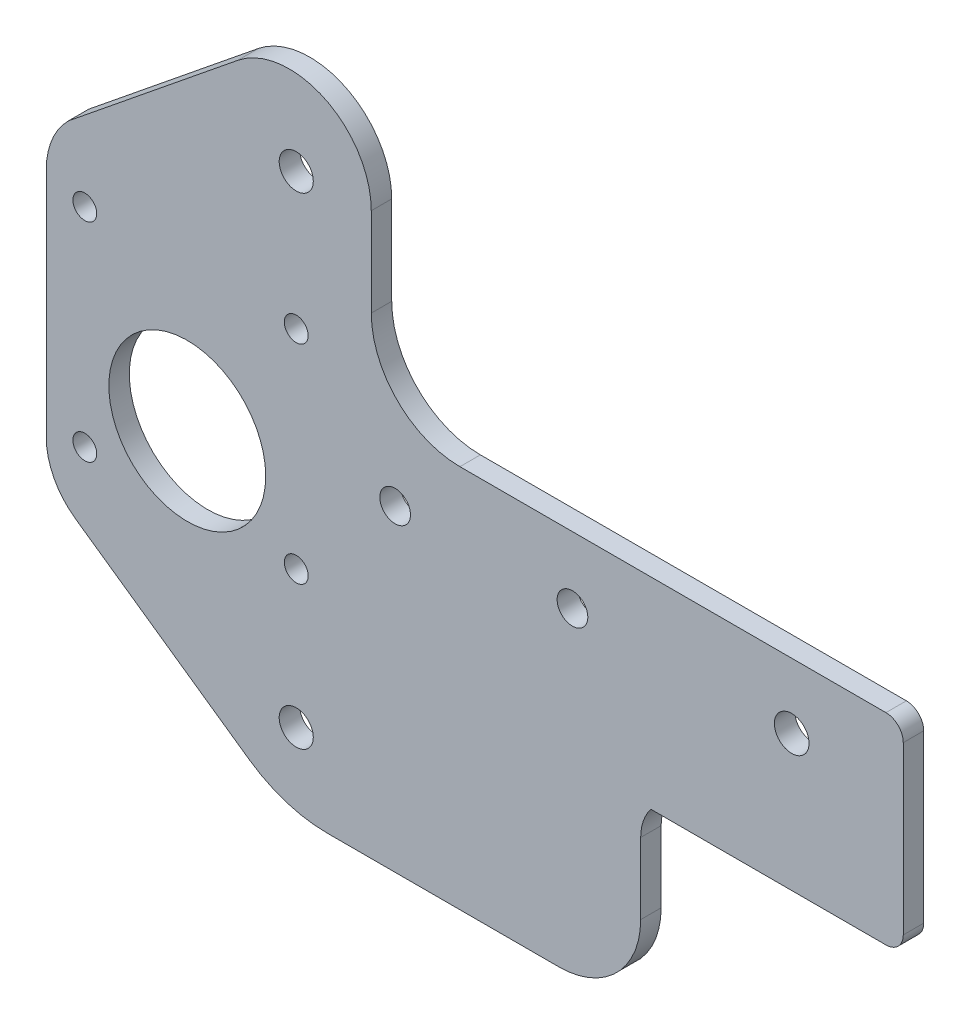
SolidWorks part; units mm, degrees
ref_plane "Front Plane" through (0, 0, 0) normal (0, 0, 1) x (1, 0, 0)
ref_plane "Top Plane" through (0, 0, 0) normal (0, 1, 0) x (1, 0, 0)
ref_plane "Right Plane" through (0, 0, 0) normal (1, 0, 0) x (0, 0, -1)
sketch "Sketch1" plane through (0, 0, 0) normal (0, 0, 1) x (1, 0, 0)
  line L0 (0, 0) -> (0, -29.5)
  line L1 (0, -29.5) -> (-37, -29.5)
  line L2 (0, 0) -> (-65, 0)
  line L3 (-78, 13) -> (-78, 26)
  line L4 (-97.5518, 35.3258) -> (-122.4205, 15.1875)
  line L5 (-125.65, 7.4017) -> (-125.65, -26.5983)
  line L6 (-89, 5.5) -> (-89, -25) construction
  line L7 (-120, 5.5) -> (-89, 5.5) construction
  line L8 (-121.3858, -34.7898) -> (-95.8858, -52.6451)
  line L9 (-84.4142, -56.2621) -> (-50.5, -56.2621)
  line L10 (-38.5, -44.2621) -> (-38.5, -33.8301)
  line L11 (-104.5, -9.75) -> (-104.5, 5.5) construction
  line L12 (-104.5, -9.75) -> (-89, -9.75) construction
  arc A0 (-78, 13) -> (-65, 0) centre (-65, 13) ccw
  arc A1 (-78, 26) -> (-97.5518, 35.3258) centre (-90, 26) ccw
  arc A2 (-122.4205, 15.1875) -> (-125.65, 7.4017) centre (-114.65, 7.4017) ccw
  arc A3 (-125.65, -26.5983) -> (-121.3858, -34.7898) centre (-115.65, -26.5983) ccw
  arc A4 (-95.8858, -52.6451) -> (-84.4142, -56.2621) centre (-84.4142, -36.2621) ccw
  arc A5 (-50.5, -56.2621) -> (-38.5, -44.2621) centre (-50.5, -44.2621) ccw
  arc A6 (-37, -29.5) -> (-38.5, -33.8301) centre (-31.5, -33.8301) ccw
  circle A7 centre (-16.356, -9.552) radius 2.54
  circle A8 centre (-48.5, -9.75) radius 2.25
  circle A9 centre (-74.5, -9.75) radius 2.25
  circle A10 centre (-89, 5.5) radius 1.75
  circle A11 centre (-89, 25.5) radius 2.5
  circle A12 centre (-89, -25) radius 1.75
  circle A13 centre (-89, -45.112) radius 2.5
  circle A14 centre (-104.975, -15.4503) radius 11.5
  circle A15 centre (-120, 5.5) radius 1.75
  circle A16 centre (-120, -25) radius 1.75
  point P18 (-104.5, 5.5)
  point P45 (0, 0)
  point P47 (-104.5, -9.75)
  point P49 (-104.5, -9.75)
  point P50 (-104.5, -9.75)
  point P51 (-104.5, -9.75)
  point P52 (-104.5, -9.75)
  point P53 (0, 0)
  point P54 (-104.5, -9.75)
  dimension "D4" = 24
  dimension "D5" = 26
  dimension "D12" = 20
  dimension "D16" = 14
  dimension "D17" = 24
  dimension "D19" = 5.08
  dimension "D20" = 4.5
  dimension "D21" = 4.5
  dimension "D22" = 31
  dimension "D23" = 5
  dimension "D25" = 5
  dimension "D11" = 3.5
  dimension "D1" = 65
  dimension "D2" = 29.5
  dimension "D3" = 37
  dimension "D6" = 13
  dimension "D7" = 32
  dimension "D8" = 51
  dimension "D10" = 34
  dimension "D14" = 125
  dimension "D15" = 25.5
  dimension "D18" = 1.5
  dimension "D29" = 72.644
  dimension "D30" = 9.75
  dimension "D31" = 9.75
  dimension "D34" = 25.5
  dimension "D37" = 70.612
  dimension "D39" = 35.56
  dimension "D40" = 48.5
  dimension "D41" = 74.5
  dimension "D42" = 89
extrude "Boss-Extrude1" add sketch "Sketch1" along normal blind 3
fillet "Fillet2" radius 2.54 2 edges at (0, 0, 1.5) (0, -29.5, 1.5)
